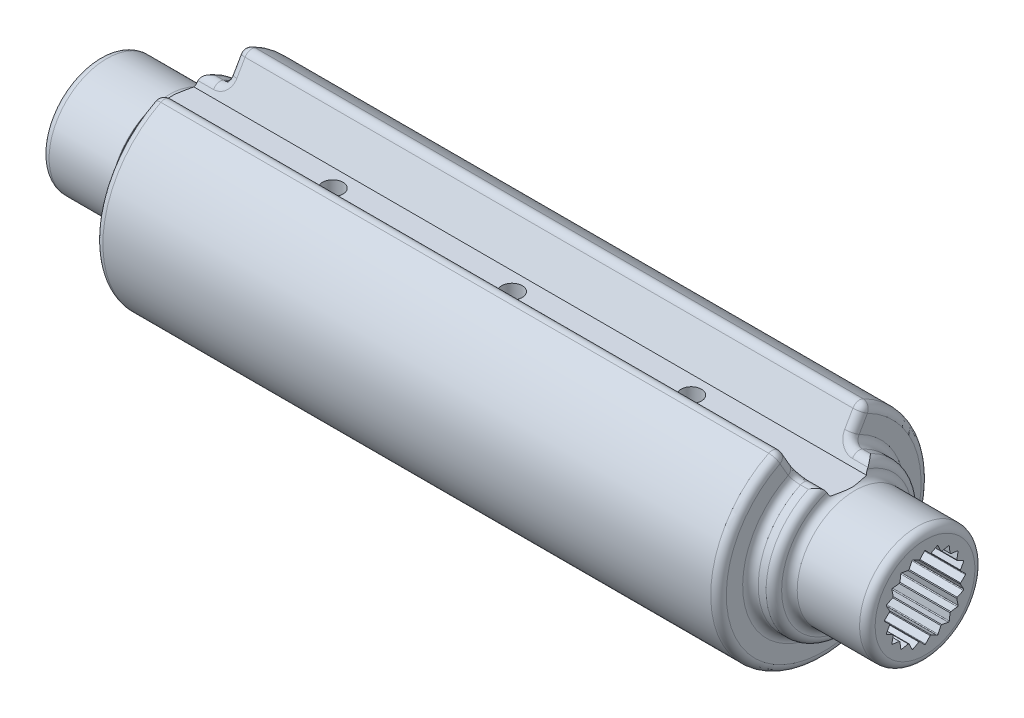
SolidWorks part; units mm, degrees
ref_plane "Front" through (0, 0, 0) normal (0, 0, 1) x (1, 0, 0)
ref_plane "Top" through (0, 0, 0) normal (0, 1, 0) x (1, 0, 0)
ref_plane "Right" through (0, 0, 0) normal (1, 0, 0) x (0, 0, -1)
sketch "Sketch1" plane through (0, 0, 0) normal (0, 1, 0) x (1, 0, 0)
  line L0 (0, 0) -> (106, 0)
  line L1 (0, 0) -> (0, 7.4)
  line L2 (0, 7.4) -> (10, 7.4)
  line L3 (10, 7.4) -> (10, 9.4)
  line L4 (10, 9.4) -> (13, 9.4)
  line L5 (13, 9.4) -> (13, 13.5)
  line L6 (13, 13.5) -> (93, 13.5)
  line L7 (53, 13.5) -> (53, 0) construction
  line L8 (93, 9.4) -> (93, 13.5)
  line L9 (96, 9.4) -> (93, 9.4)
  line L10 (96, 7.4) -> (96, 9.4)
  line L11 (106, 7.4) -> (96, 7.4)
  line L12 (106, 0) -> (106, 7.4)
  dimension "D1" = 7.4
  dimension "D2" = 10
  dimension "D3" = 2
  dimension "D4" = 3
  dimension "D5" = 13.5
  dimension "D6" = 40
revolve "Revolve1" add sketch "Sketch1" angle 360 about L0
sketch "Sketch2" plane through (13, 0, 0) normal (-1, 0, 0) x (0, 0, 1)
  line L0 (-2.3373, 7.5) -> (2.3373, 7.5)
  line L4 (-5.2, 12.4583) -> (0, 3.4517)
  line L5 (0, 3.4517) -> (5.2, 12.4583)
  line L6 (5.2, 12.4583) -> (-5.2, 12.4583)
  line L7 (0, 13.5) -> (0, 7.5) construction
  circle A4 centre (0, 0) radius 13.5
  circle A5 centre (0, 0) radius 13.5 construction
  circle A6 centre (0, 9.4561) radius 3.0022 construction
  circle M5 centre (0, 0) radius 9.4
  circle M6 centre (0, 0) radius 13.5
  dimension "D2" = 6
  dimension "D1" = 10.4
extrude "Cut-Extrude1" cut sketch "Sketch2" against normal through all both and the other way through all flip side to cut contours L5 L4 M5 M6 | L5 L4 M5 | L4 L5 L0 region at (13, 6.1506, 0) region at (13, -0.541, 0) region at (13, -7.9784, -5.6469)
sketch "Sketch3" plane through (0, 7.5, 2) normal (0, -1, 0) x (1, 0, 0)
  line L0 (10, -2) -> (96, -2) construction
  line L1 (96, -9.4) -> (96, 5.4) construction
  line L3 (30, -2) -> (53, -2) construction
  line L4 (10, 0.3373) -> (10, -4.3373) construction
  circle A0 centre (30, -2) radius 1.315
  circle A1 centre (53, -2) radius 1.315
  circle A2 centre (76, -2) radius 1.315
  point P9 (53, -2)
  dimension "D1" = 2.63
  dimension "D4" = 23
  dimension "D3" = 3
extrude "Cut-Extrude2" cut sketch "Sketch3" along normal through all
sketch "Sketch4" plane through (106, 0, 0) normal (-1, 0, 0) x (0, 0, 1)
  line L0 (-0.66, 4.5625) -> (-0.0731, 5.1916)
  line L1 (0.0731, 5.1916) -> (0.66, 4.5625)
  line L2 (0.7822, 4.5432) -> (1.5348, 4.9601)
  line L3 (1.6738, 4.9149) -> (2.0376, 4.1353)
  line L4 (2.1478, 4.0791) -> (2.9924, 4.2431)
  line L5 (3.1107, 4.1571) -> (3.2157, 3.3032)
  line L6 (3.3032, 3.2157) -> (4.1571, 3.1107)
  line L7 (4.2431, 2.9924) -> (4.0791, 2.1478)
  line L8 (4.1353, 2.0376) -> (4.9149, 1.6738)
  line L9 (4.9601, 1.5348) -> (4.5432, 0.7822)
  line L10 (4.5625, 0.66) -> (5.1916, 0.0731)
  line L11 (5.1916, -0.0731) -> (4.5625, -0.66)
  line L12 (4.5432, -0.7822) -> (4.9601, -1.5348)
  line L13 (4.9149, -1.6738) -> (4.1353, -2.0376)
  line L14 (4.0791, -2.1478) -> (4.2431, -2.9924)
  line L15 (4.1571, -3.1107) -> (3.3032, -3.2157)
  line L16 (3.2157, -3.3032) -> (3.1107, -4.1571)
  line L17 (2.9924, -4.2431) -> (2.1478, -4.0791)
  line L18 (2.0376, -4.1353) -> (1.6738, -4.9149)
  line L19 (1.5348, -4.9601) -> (0.7822, -4.5432)
  line L20 (0.66, -4.5625) -> (0.0731, -5.1916)
  line L21 (-0.0731, -5.1916) -> (-0.66, -4.5625)
  line L22 (-0.7822, -4.5432) -> (-1.5348, -4.9601)
  line L23 (-1.6738, -4.9149) -> (-2.0376, -4.1353)
  line L24 (-2.1478, -4.0791) -> (-2.9924, -4.2431)
  line L25 (-3.1107, -4.1571) -> (-3.2157, -3.3032)
  line L26 (-3.3032, -3.2157) -> (-4.1571, -3.1107)
  line L27 (-4.2431, -2.9924) -> (-4.0791, -2.1478)
  line L28 (-4.1353, -2.0376) -> (-4.9149, -1.6738)
  line L29 (-4.9601, -1.5348) -> (-4.5432, -0.7822)
  line L30 (-4.5625, -0.66) -> (-5.1916, -0.0731)
  line L31 (-5.1916, 0.0731) -> (-4.5625, 0.66)
  line L32 (-4.5432, 0.7822) -> (-4.9601, 1.5348)
  line L33 (-4.9149, 1.6738) -> (-4.1353, 2.0376)
  line L34 (-4.0791, 2.1478) -> (-4.2431, 2.9924)
  line L35 (-4.1571, 3.1107) -> (-3.3032, 3.2157)
  line L36 (-3.2157, 3.3032) -> (-3.1107, 4.1571)
  line L37 (-2.9924, 4.2431) -> (-2.1478, 4.0791)
  line L38 (-2.0376, 4.1353) -> (-1.6738, 4.9149)
  line L39 (-1.5348, 4.9601) -> (-0.7822, 4.5432)
  arc A0 (-3.2157, 3.3032) -> (-3.3032, 3.2157) centre (0, 0) ccw
  arc A1 (-0.0731, 5.1916) -> (0.0731, 5.1916) centre (0, 5.1234) cw
  arc A2 (1.5348, 4.9601) -> (1.6738, 4.9149) centre (1.5832, 4.8726) cw
  arc A3 (2.9924, 4.2431) -> (3.1107, 4.1571) centre (3.0115, 4.1449) cw
  arc A4 (4.1571, 3.1107) -> (4.2431, 2.9924) centre (4.1449, 3.0115) cw
  arc A5 (4.9149, 1.6738) -> (4.9601, 1.5348) centre (4.8726, 1.5832) cw
  arc A6 (5.1916, 0.0731) -> (5.1916, -0.0731) centre (5.1234, 0) cw
  arc A7 (4.9601, -1.5348) -> (4.9149, -1.6738) centre (4.8726, -1.5832) cw
  arc A8 (4.2431, -2.9924) -> (4.1571, -3.1107) centre (4.1449, -3.0115) cw
  arc A9 (3.1107, -4.1571) -> (2.9924, -4.2431) centre (3.0115, -4.1449) cw
  arc A10 (1.6738, -4.9149) -> (1.5348, -4.9601) centre (1.5832, -4.8726) cw
  arc A11 (0.0731, -5.1916) -> (-0.0731, -5.1916) centre (0, -5.1234) cw
  arc A12 (-1.5348, -4.9601) -> (-1.6738, -4.9149) centre (-1.5832, -4.8726) cw
  arc A13 (-2.9924, -4.2431) -> (-3.1107, -4.1571) centre (-3.0115, -4.1449) cw
  arc A14 (-4.1571, -3.1107) -> (-4.2431, -2.9924) centre (-4.1449, -3.0115) cw
  arc A15 (-4.9149, -1.6738) -> (-4.9601, -1.5348) centre (-4.8726, -1.5832) cw
  arc A16 (-5.1916, -0.0731) -> (-5.1916, 0.0731) centre (-5.1234, 0) cw
  arc A17 (-4.9601, 1.5348) -> (-4.9149, 1.6738) centre (-4.8726, 1.5832) cw
  arc A18 (-4.2431, 2.9924) -> (-4.1571, 3.1107) centre (-4.1449, 3.0115) cw
  arc A19 (-3.1107, 4.1571) -> (-2.9924, 4.2431) centre (-3.0115, 4.1449) cw
  arc A20 (-1.6738, 4.9149) -> (-1.5348, 4.9601) centre (-1.5832, 4.8726) cw
  arc A21 (-2.0376, 4.1353) -> (-2.1478, 4.0791) centre (0, 0) ccw
  arc A22 (-0.66, 4.5625) -> (-0.7822, 4.5432) centre (0, 0) ccw
  arc A23 (0.7822, 4.5432) -> (0.66, 4.5625) centre (0, 0) ccw
  arc A24 (2.1478, 4.0791) -> (2.0376, 4.1353) centre (0, 0) ccw
  arc A25 (3.3032, 3.2157) -> (3.2157, 3.3032) centre (0, 0) ccw
  arc A26 (4.1353, 2.0376) -> (4.0791, 2.1478) centre (0, 0) ccw
  arc A27 (4.5625, 0.66) -> (4.5432, 0.7822) centre (0, 0) ccw
  arc A28 (4.5432, -0.7822) -> (4.5625, -0.66) centre (0, 0) ccw
  arc A29 (4.0791, -2.1478) -> (4.1353, -2.0376) centre (0, 0) ccw
  arc A30 (3.2157, -3.3032) -> (3.3032, -3.2157) centre (0, 0) ccw
  arc A31 (2.0376, -4.1353) -> (2.1478, -4.0791) centre (0, 0) ccw
  arc A32 (0.66, -4.5625) -> (0.7822, -4.5432) centre (0, 0) ccw
  arc A33 (-0.7822, -4.5432) -> (-0.66, -4.5625) centre (0, 0) ccw
  arc A34 (-2.1478, -4.0791) -> (-2.0376, -4.1353) centre (0, 0) ccw
  arc A35 (-3.3032, -3.2157) -> (-3.2157, -3.3032) centre (0, 0) ccw
  arc A36 (-4.1353, -2.0376) -> (-4.0791, -2.1478) centre (0, 0) ccw
  arc A37 (-4.5625, -0.66) -> (-4.5432, -0.7822) centre (0, 0) ccw
  arc A38 (-4.5432, 0.7822) -> (-4.5625, 0.66) centre (0, 0) ccw
  arc A39 (-4.0791, 2.1478) -> (-4.1353, 2.0376) centre (0, 0) ccw
  point P10 (0, 5.27)
  point P107 (0, 0)
  dimension "D1" = 9.22
  dimension "D5" = 0.1
  dimension "D2" = 5.27
  dimension "D3" = 0.66
  dimension "D4" = 0.66
  dimension "D6" = 20
extrude "Cut-Extrude4" cut sketch "Sketch4" along normal blind 16
fillet "Fillet1" radius 1 20 edges at (106, 0, 7.4) (96, 0, 7.4) (96, -9.4, 0) (93, -9.4, 0) (93, -13.5, 0) (0, 0, 7.4) (13, -9.4, 0) (13, -13.5, 0) (10, -9.4, 0) (10, 0, 7.4) (94.5, 8.8652, -3.1255) (94.5, 8.8652, 3.1255) (11.5, 8.8652, -3.1255) (11.5, 8.8652, 3.1255) (93, 10.6618, -4.1627) (93, 10.6618, 4.1627) (13, 10.6618, -4.1627) (13, 10.6618, 4.1627) (53, 12.4583, 5.2) (53, 12.4583, -5.2)
